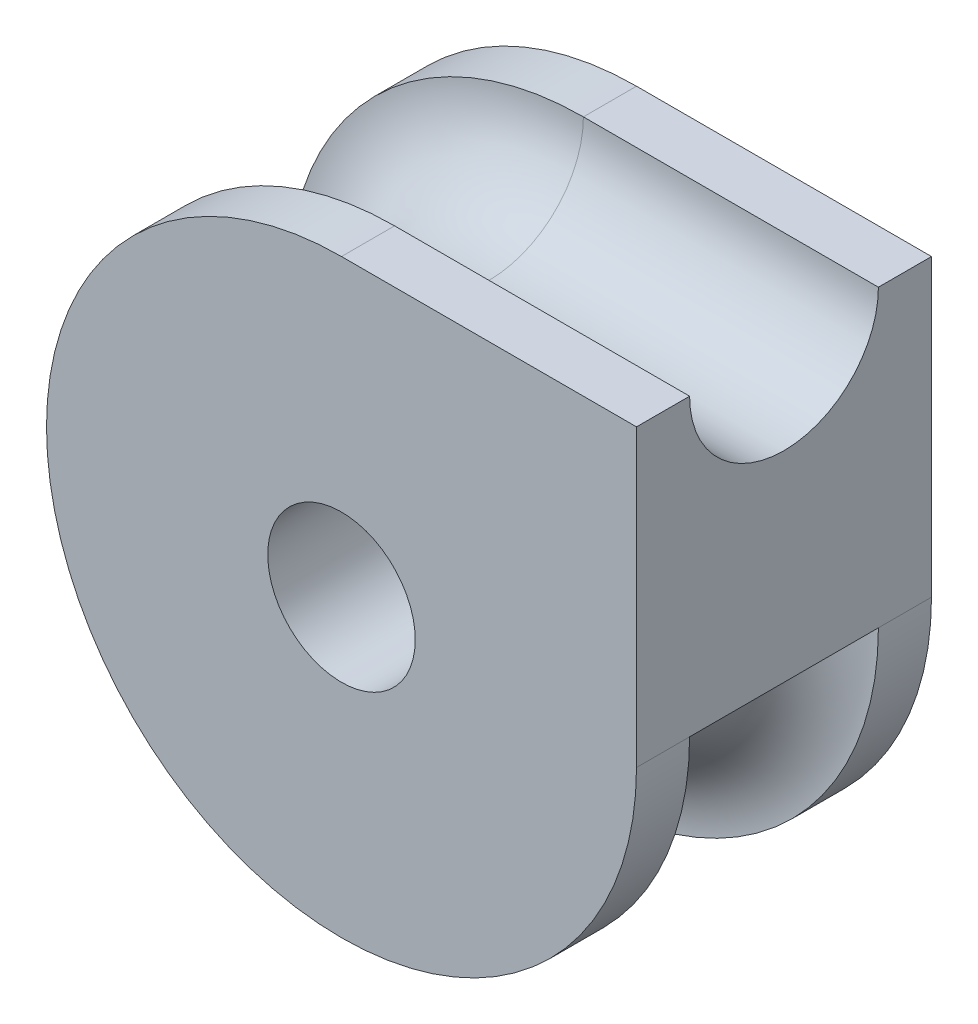
SolidWorks part; units mm, degrees
ref_plane "Front Plane" through (0, 0, 0) normal (0, 0, 1) x (1, 0, 0)
ref_plane "Top Plane" through (0, 0, 0) normal (0, 1, 0) x (1, 0, 0)
ref_plane "Right Plane" through (0, 0, 0) normal (1, 0, 0) x (0, 0, -1)
sketch "Sketch1" plane through (0, 0, 0) normal (0, 0, 1) x (1, 0, 0)
  line L0 (0, 50) -> (50, 50)
  line L1 (50, 50) -> (50, 0)
  arc A0 (0, 50) -> (50, 0) centre (0, 0) ccw
  circle A1 centre (0, 0) radius 12.5
  dimension "D1" = 50
  dimension "D2" = 25
extrude "Boss-Extrude2" add sketch "Sketch1" along normal blind 50
sketch "Sketch2" plane through (0, 0, 0) normal (1, 0, 0) x (0, 0, -1)
  line L0 (0, 0) -> (-64.6586, 0) construction
  line L1 (-50, 50) -> (0, 50) construction
  line L2 (-41, 50) -> (-9, 50)
  arc A0 (-41, 50) -> (-9, 50) centre (-25, 50) ccw
  point P6 (0, 0)
  point P7 (0, 0)
  point P9 (-17.711, 50)
  point P12 (-25, 50)
  dimension "D1" = 16
revolve "Cut-Revolve1" cut sketch "Sketch2" angle 270 about L0
extrude "Cut-Extrude1" cut sketch "Sketch2<2>" along normal blind 50
sketch "Sketch2<2>" plane through (0, 0, 0) normal (1, 0, 0) x (0, 0, -1) same geometry as "Sketch2"
